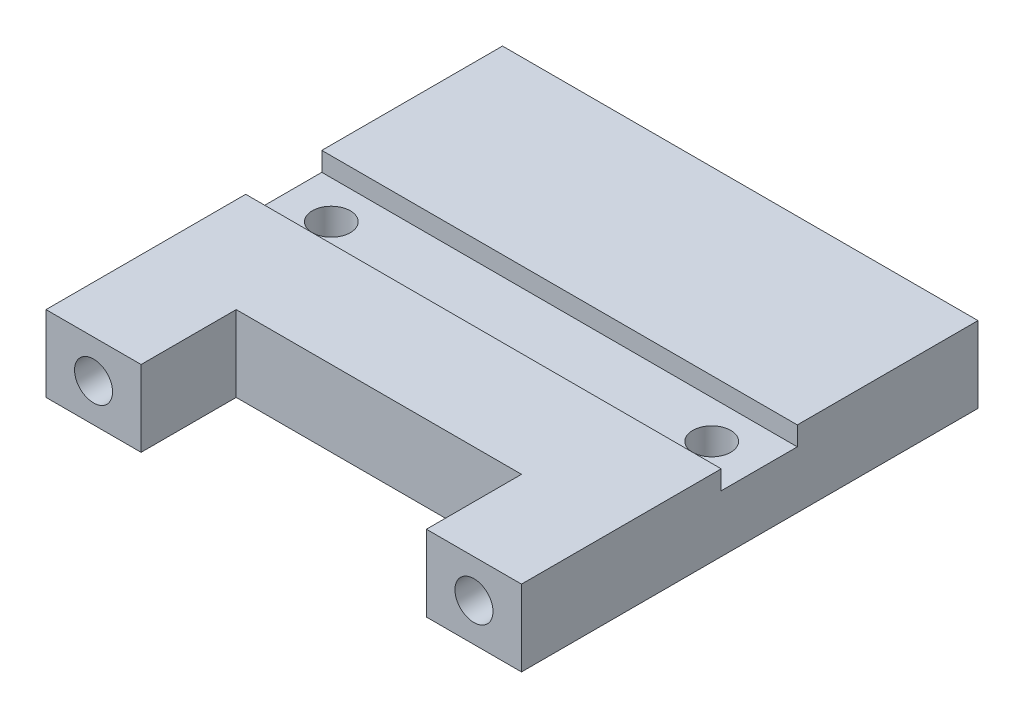
SolidWorks part; units mm, degrees
material "PVC rigide"
ref_plane "Plan de face" through (0, 0, 0) normal (0, 0, 1) x (1, 0, 0)
ref_plane "Plan de dessus" through (0, 0, 0) normal (0, 1, 0) x (1, 0, 0)
ref_plane "Plan de droite" through (0, 0, 0) normal (1, 0, 0) x (0, 0, -1)
sketch "Esquisse1" plane through (0, 0, 0) normal (0, 1, 0) x (1, 0, 0)
  line L0 (-47.1481, -1.9583) -> (-47.1481, 8.0417)
  line L1 (-57.1481, 46.0417) -> (-7.1481, 46.0417)
  line L2 (-57.1481, 46.0417) -> (-57.1481, -1.9583)
  line L3 (-57.1481, -1.9583) -> (-47.1481, -1.9583)
  line L4 (-7.1481, 46.0417) -> (-7.1481, 16.0417)
  line L5 (-47.1481, 8.0417) -> (-17.1481, 8.0417)
  line L6 (-17.1481, 8.0417) -> (-17.1481, -1.9583)
  line L7 (-17.1481, -1.9583) -> (-7.1481, -1.9583)
  line L8 (-7.1481, -1.9583) -> (-7.1481, 16.0417)
  dimension "D1" = 50
  dimension "D2" = 48
  dimension "D3" = 10
  dimension "D5" = 10
extrude "Boss.-Extru.1" add sketch "Esquisse1" along normal blind 8
sketch "Esquisse2" plane through (0, 0, 1.9583) normal (0, 0, 1) x (1, 0, 0)
  line L0 (-57.1481, 8) -> (-47.1481, 0) construction
  line L1 (-57.1481, 0) -> (-47.1481, 8) construction
  line L2 (-17.1481, 8) -> (-7.1481, 0) construction
  line L3 (-17.1481, 0) -> (-7.1481, 8) construction
  line L4 (-47.1481, 8) -> (-17.1481, 8) construction
  line L5 (-17.1481, 8) -> (-17.1481, 0) construction
  circle A0 centre (-52.1481, 4) radius 2
  circle A1 centre (-12.1481, 4) radius 2
  point P8 (-52.1481, 4)
  point P15 (-12.1481, 4)
  dimension "D1" = 4
extrude "Enlèv. mat.-Extru.1" cut sketch "Esquisse2" against normal blind 10
sketch "Esquisse3" plane through (0, 0, -46.0417) normal (0, 0, -1) x (-1, 0, 0)
  line L0 (7.1481, 4) -> (57.1481, 4) construction
  line L1 (7.1481, 8) -> (7.1481, 0) construction
  line L2 (57.1481, 8) -> (57.1481, 0) construction
  circle A0 centre (12.1481, 4) radius 2
  circle A1 centre (52.1481, 4) radius 2
  dimension "D1" = 4
  dimension "D2" = 5
  dimension "D3" = 5
extrude "Enlèv. mat.-Extru.2" cut sketch "Esquisse3" against normal blind 10
sketch "Esquisse4" plane through (0, 8, 0) normal (0, 1, 0) x (1, 0, 0)
  line L0 (-62.8741, 23.0417) -> (2.0024, 23.0417) construction
  line L1 (-7.1481, 46.0417) -> (-57.1481, 46.0417) construction
  line L2 (-57.1481, 46.0417) -> (-57.1481, -1.9583) construction
  line L3 (-7.1481, -1.9583) -> (-7.1481, 46.0417) construction
  circle A0 centre (-52.1481, 23.0417) radius 2
  circle A1 centre (-12.1481, 23.0417) radius 2
  dimension "D2" = 4
  dimension "D1" = 23
  dimension "D3" = 5
  dimension "D4" = 5
extrude "Enlèv. mat.-Extru.3" cut sketch "Esquisse4" against normal blind 10
chamfer "Chanfrein1" distance 2.5 angle 45 2 edges at (-52.1481, 0, -21.0417) (-12.1481, 0, -21.0417)
sketch "Esquisse5" plane through (0, 8, 0) normal (0, 1, 0) x (1, 0, 0)
  line L0 (-57.1481, 46.0417) -> (-57.1481, -1.9583) construction
  line L1 (-57.1481, 27.0417) -> (-7.1481, 27.0417)
  line L2 (-57.1481, 27.0417) -> (-57.1481, 19.0417)
  line L3 (-57.1481, 19.0417) -> (-7.1481, 19.0417)
  line L4 (-7.1481, 27.0417) -> (-7.1481, 19.0417)
  line L5 (-7.1481, -1.9583) -> (-7.1481, 46.0417) construction
  circle A0 centre (-52.1481, 23.0417) radius 2 construction
  dimension "D1" = 4
  dimension "D2" = 8
extrude "Enlèv. mat.-Extru.4" cut sketch "Esquisse5" against normal blind 2
